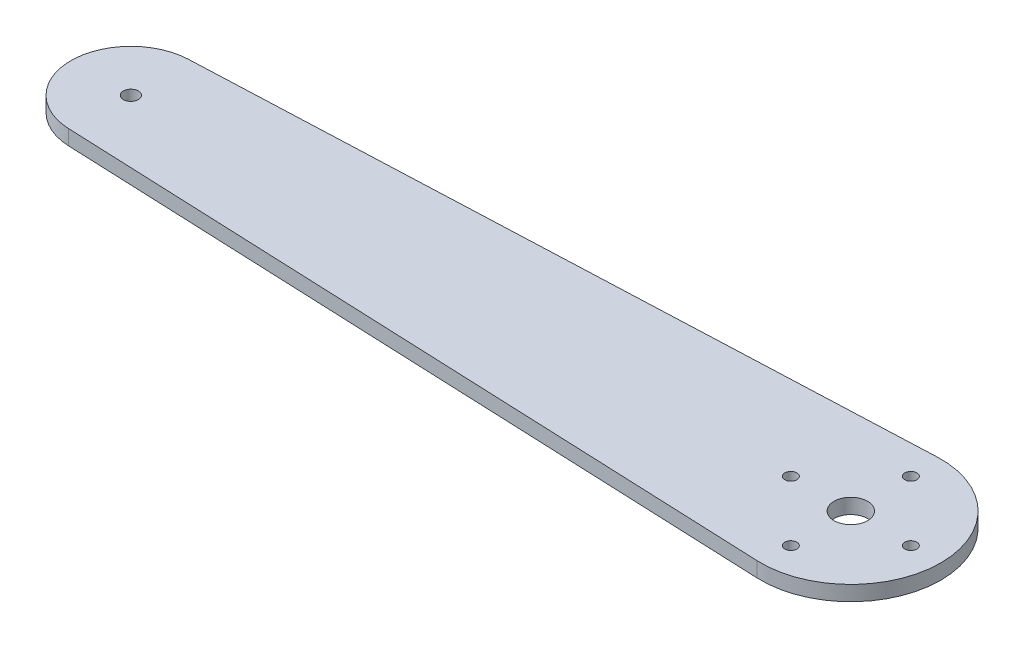
SolidWorks part; units mm, degrees
ref_plane "Front Plane" through (0, 0, 0) normal (0, 0, 1) x (1, 0, 0)
ref_plane "Top Plane" through (0, 0, 0) normal (0, 1, 0) x (1, 0, 0)
ref_plane "Right Plane" through (0, 0, 0) normal (1, 0, 0) x (0, 0, -1)
sketch "Sketch1" plane through (0, 0, 0) normal (0, 1, 0) x (1, 0, 0)
  line L0 (-152.9292, 12.689) -> (-0.7938, 19.0335)
  line L1 (-152.9292, -12.689) -> (-0.7937, -19.0335)
  line L2 (-111.3601, 0) -> (-50111.3601, 0) construction
  line L3 (0, -984.3615) -> (0, 49015.6385) construction
  line L4 (0, 0) -> (0, 12.7) construction
  line L5 (0, 0) -> (12.7, 0) construction
  arc A0 (-0.7937, -19.0335) -> (-0.7938, 19.0335) centre (0, 0) ccw
  arc A1 (-152.9292, 12.689) -> (-152.9292, -12.689) centre (-152.4, 0) ccw
  circle A2 centre (-152.4, 0) radius 1.5875
  circle A3 centre (0, 0) radius 3.556
  circle A4 centre (0, 12.7) radius 1.27
  circle A5 centre (12.7, 0) radius 1.27
  circle A6 centre (0, -12.7) radius 1.27
  circle A7 centre (-12.7, 0) radius 1.27
  dimension "D1" = 12.7
  dimension "D2" = 19.05
  dimension "D4" = 3.175
  dimension "D5" = 7.112
  dimension "D6" = 2.54
  dimension "D3" = 152.4
  dimension "D7" = 12.7
  dimension "D9" = 90
  dimension "D10" = 12.7
  dimension "D8" = 4
extrude "Boss-Extrude1" add sketch "Sketch1" along normal blind 3.175
